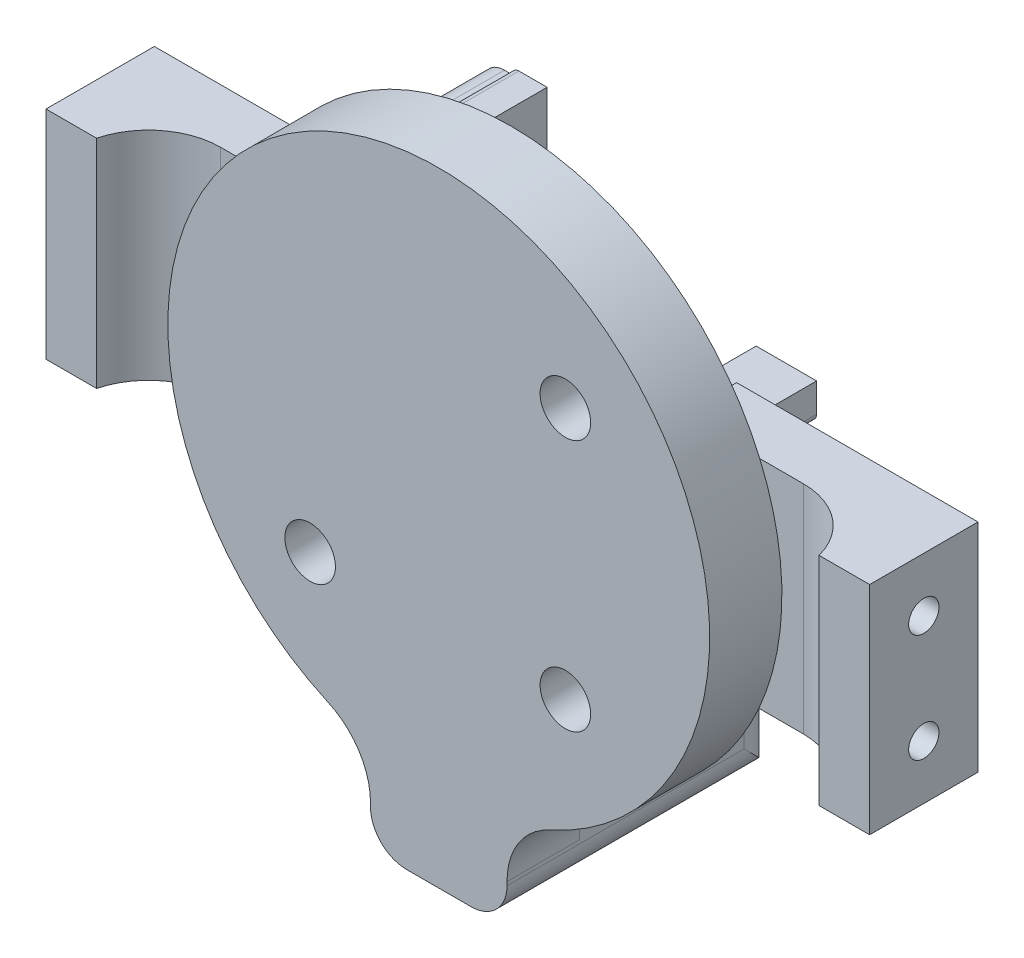
SolidWorks part; units mm, degrees
material "ABS"
ref_plane "Front Plane" through (0, 0, 0) normal (0, 0, 1) x (1, 0, 0)
ref_plane "Top Plane" through (0, 0, 0) normal (0, 1, 0) x (1, 0, 0)
ref_plane "Right Plane" through (0, 0, 0) normal (1, 0, 0) x (0, 0, -1)
sketch "Sketch1" plane through (0, 0, 0) normal (0, 0, 1) x (1, 0, 0)
  line L0 (-17.8145, -17.5408) -> (17.5408, 17.8145)
  line L1 (17.5408, -17.5408) -> (-17.8145, 17.8145)
  circle A0 centre (-0.1369, 0.1369) radius 37.5
  point P0 (17.5408, -17.5408)
  point P1 (-17.8145, -17.5408)
  point P2 (17.5408, 17.8145)
  point P3 (-17.8145, 17.8145)
  dimension "D3" = 75
  dimension "D1" = 35.3553
  dimension "D2" = 35.3553
extrude "Boss-Extrude1" add sketch "Sketch1" along normal blind 10
hole_wizard "CSK for M6 Hex Socket Countersunk Cap Screw1" positions "Sketch4" profile "Sketch5" countersink size "M6" standard "ISO"
sketch "Sketch4" plane through (0, 0, 0) normal (0, 0, -1) x (-1, 0, 0)
  point P0 (-17.3883, 17.5895)
  point P4 (-17.3883, -17.337)
  point P6 (17.9415, -17.337)
sketch "Sketch5" plane through (17.3883, 17.5895, 0) normal (1, 0, 0) x (0, 1, 0)
  line L0 (0, 0) -> (0, 16.543)
  line L1 (0, 16.543) -> (3.5, 14.44)
  line L2 (3.5, 14.44) -> (3.5, 3.22)
  line L3 (3.5, 3.22) -> (6.72, 0)
  line L5 (6.72, 0) -> (0, 0)
  line L6 (-3.5, 3.22) -> (-6.72, 0) construction
  line L10 (0, 16.543) -> (-3.5, 14.44) construction
  line L11 (0, -6.35) -> (0, 107.95) construction
  dimension "Hole Dia." = 7
  dimension "Hole Depth" = 14.44
  dimension "Near C'Sink Dia." = 13.44
  dimension "Near C'Sink Angle" = 90
  dimension "Drill Angle" = 118
ref_plane "Plane1" through (50, 0, 0) normal (1, 0, 0) x (0, 0, -1)
ref_plane "Plane2" through (-50, 0, 0) normal (1, 0, 0) x (0, 0, -1)
sketch "Sketch6" plane through (50, 0, 0) normal (1, 0, 0) x (0, 0, -1)
  line L1 (-7.5, -15) -> (7.5, -15)
  line L2 (-7.5, -15) -> (-7.5, 15)
  line L3 (-7.5, 15) -> (7.5, 15)
  line L4 (7.5, -15) -> (7.5, 15)
  line L5 (-7.5, -15) -> (7.5, 15) construction
  line L6 (-7.5, 15) -> (7.5, -15) construction
  point P0 (0, 0)
  dimension "D1" = 30
  dimension "D2" = 15
extrude "Boss-Extrude2" add sketch "Sketch6" along normal blind 7 separate body
sketch "Sketch7" plane through (-50, 0, 0) normal (1, 0, 0) x (0, 0, -1)
  line L4 (7.5, -15) -> (7.5, 15)
  line L5 (-7.5, -15) -> (7.5, -15)
  line L6 (-7.5, 15) -> (-7.5, -15)
  line L7 (7.5, 15) -> (-7.5, 15)
  line L8 (7.5, -15) -> (7.5, 15)
  line L9 (-7.5, -15) -> (7.5, -15)
  line L10 (-7.5, 15) -> (-7.5, -15)
  line L11 (7.5, 15) -> (-7.5, 15)
  dimension "D1" = 0
extrude "Boss-Extrude3" add sketch "Sketch7" against normal blind 7 separate body
sketch "Sketch8" plane through (0, 0, -7.5) normal (0, 0, -1) x (-1, 0, 0)
  line L0 (-57, 15) -> (-23.5894, 15)
  line L1 (24.1425, 15) -> (11.7405, 15)
  line L4 (57, -15) -> (57, 15) construction
  line L5 (57, -15) -> (24.242, -15)
  line L6 (-57, -15) -> (-57, 15) construction
  line L7 (-57, -15) -> (-57, 15)
  line L8 (57, -15) -> (57, 15)
  line L9 (-11.1873, 15) -> (11.7405, 15)
  line L10 (24.1425, 15) -> (57, 15)
  line L11 (11.641, -15) -> (-11.0878, -15)
  line L12 (-23.6889, -15) -> (-57, -15)
  circle A0 centre (0.1369, 0.1369) radius 37.5 construction
  circle A1 centre (-17.3883, -17.337) radius 6.72 construction
  circle A2 centre (17.9415, -17.337) radius 6.72 construction
  circle A4 centre (-17.3883, 17.5895) radius 6.72 construction
  arc A5 (-34.1724, -15) -> (34.4461, -15) centre (0.1369, 0.1369) ccw
  circle A6 centre (-17.3883, -17.337) radius 6.72
  circle A7 centre (17.9415, -17.337) radius 6.72
  circle A9 centre (-17.3883, 17.5895) radius 6.72
  arc A10 (34.5656, 15) -> (-34.2919, 15) centre (0.1369, 0.1369) ccw
  line M6 (-50, -15) -> (-50, 15)
  line M7 (-50, 15) -> (-57, 15)
  line M8 (-57, 15) -> (-57, -15)
  line M9 (-57, -15) -> (-50, -15)
extrude "Boss-Extrude4" add sketch "Sketch8" against normal up to surface (7.5 mm away) contours M9 M6 M7 M8 | A9 L0 L12 A6 L11 A7 L5 L8 L10 L9 M6 region at (53.5, 0, -7.5) region at (-3.8337, 0.1834, -7.5) up to face at (10.6683, 17.5895, 0)
fillet "Fillet1" radius 10 2 edges at (-50, 0, 0) (50, 0, 0)
sketch "Sketch9" plane through (57, 0, 0) normal (1, 0, 0) x (0, 0, -1)
  line L0 (7.5, 15) -> (7.5, -15) construction
  circle A0 centre (0, -7.5) radius 2.1
  circle A1 centre (0, 7.5) radius 2.1
  point P7 (7.5, 0)
  dimension "D1" = 4.2
  dimension "D2" = 4.2
  dimension "D3" = 15
  dimension "D4" = 7.5
extrude "Cut-Extrude1" cut sketch "Sketch9" against normal blind 6
mirror "Mirror1" about plane through (0, 0, 0) normal (1, 0, 0) of "Cut-Extrude1"
sketch "Sketch11" plane through (0, 0, -7.5) normal (0, 0, -1) x (-1, 0, 0)
  line L0 (27.6369, 7.3869) -> (27.6369, 12.2869)
  line L1 (27.6369, -7.1131) -> (27.6369, -12.0131)
  line L2 (31.5369, 12.2869) -> (27.6369, 12.2869)
  line L3 (0.4369, -7.1131) -> (0.4369, -12.0131)
  line L26 (-4.856, -12.656) -> (-3.5119, -12.656)
  line L27 (-1.656, -12.0131) -> (31.5369, -12.0131)
  line L28 (32.5369, -11.0131) -> (33.5369, -11.0131)
  line L29 (36.5369, -8.0131) -> (36.5369, -6.0131)
  line L30 (33.5369, -3.0131) -> (32.5369, -3.0131)
  line L31 (32.5369, -3.0131) -> (32.5369, 3.3869)
  line L32 (32.5369, 3.3869) -> (33.5369, 3.3869)
  line L33 (36.5369, 6.3869) -> (36.5369, 8.3869)
  line L34 (33.5369, 11.3869) -> (32.5318, 11.3869)
  line L35 (31.5369, 12.2869) -> (20.3869, 12.2869)
  line L36 (20.3869, 12.2869) -> (20.3869, 20.9869)
  line L37 (18.3246, 24.4862) -> (10.718, 26.0155)
  line L38 (1.0557, 26.0155) -> (-6.5509, 24.4862)
  line L39 (-8.6131, 20.9869) -> (-8.6131, 9.5369)
  line L40 (-8.6131, 9.5369) -> (-8.6631, 9.5369)
  line L41 (-9.6631, 8.5369) -> (-9.6631, 4.5369)
  line L42 (-9.6631, 4.5369) -> (0.4369, 4.5369)
  line L43 (0.4369, 4.5369) -> (0.4369, 6.7056)
  line L44 (12.1987, 7.3869) -> (27.6369, 7.3869)
  line L45 (27.6369, 7.3869) -> (27.6369, -7.1131)
  line L46 (27.6369, -7.1131) -> (0.4369, -7.1131)
  line L47 (0.4369, -7.1131) -> (0.4369, -4.2631)
  line L48 (0.4369, -4.2631) -> (-9.6631, -4.2631)
  line L49 (-9.6631, -4.2631) -> (-9.6631, -8.2631)
  line L50 (-8.6631, -9.2631) -> (-7.856, -9.2631)
  line L51 (-7.856, -9.2631) -> (-7.856, -9.656)
  line L52 (-4.856, -12.656) -> (-3.5119, -12.656)
  line L53 (-1.656, -12.0131) -> (31.5369, -12.0131)
  line L54 (32.5369, -11.0131) -> (33.5369, -11.0131)
  line L55 (36.5369, -8.0131) -> (36.5369, -6.0131)
  line L56 (33.5369, -3.0131) -> (32.5369, -3.0131)
  line L57 (32.5369, -3.0131) -> (32.5369, 3.3869)
  line L58 (32.5369, 3.3869) -> (33.5369, 3.3869)
  line L59 (36.5369, 6.3869) -> (36.5369, 8.3869)
  line L60 (33.5369, 11.3869) -> (32.5318, 11.3869)
  line L71 (27.6369, 7.3869) -> (27.6369, -7.1131)
  line L72 (27.6369, -7.1131) -> (0.4369, -7.1131)
  line L73 (0.4369, -7.1131) -> (0.4369, -4.2631)
  line L74 (0.4369, -4.2631) -> (-9.6631, -4.2631)
  line L75 (-9.6631, -4.2631) -> (-9.6631, -8.2631)
  line L76 (-8.6631, -9.2631) -> (-7.856, -9.2631)
  line L77 (-7.856, -9.2631) -> (-7.856, -9.656)
  circle A0 centre (-4.017, -8.5603) radius 1.8 construction
  circle A1 centre (32.4372, 7.3869) radius 1.8 construction
  circle A2 centre (32.4372, -7.0131) radius 1.8 construction
  circle A3 centre (-4.017, -8.5603) radius 1.8
  circle A4 centre (32.4372, 7.3869) radius 1.8
  circle A5 centre (32.4372, -7.0131) radius 1.8
  circle A6 centre (32.4372, -7.0131) radius 2.1
  circle A7 centre (32.4372, 7.3869) radius 2.1
  circle A8 centre (-4.017, -8.5603) radius 2.1
  arc A14 (-3.5119, -12.656) -> (-1.656, -12.0131) centre (-3.5119, -9.656) ccw
  arc A15 (31.5369, -12.0131) -> (32.5369, -11.0131) centre (31.5369, -11.0131) ccw
  arc A16 (33.5369, -11.0131) -> (36.5369, -8.0131) centre (33.5369, -8.0131) ccw
  arc A17 (36.5369, -6.0131) -> (33.5369, -3.0131) centre (33.5369, -6.0131) ccw
  arc A18 (33.5369, 3.3869) -> (36.5369, 6.3869) centre (33.5369, 6.3869) ccw
  arc A19 (36.5369, 8.3869) -> (33.5369, 11.3869) centre (33.5369, 8.3869) ccw
  arc A20 (32.5318, 11.3869) -> (31.5369, 12.2869) centre (31.5369, 11.2869) ccw
  arc A21 (20.3869, 20.9869) -> (18.3246, 24.4862) centre (16.3869, 20.9869) ccw
  arc A22 (10.718, 26.0155) -> (1.0557, 26.0155) centre (5.8869, 14.4869) ccw
  arc A23 (-6.5509, 24.4862) -> (-8.6131, 20.9869) centre (-4.6131, 20.9869) ccw
  arc A24 (-8.6631, 9.5369) -> (-9.6631, 8.5369) centre (-8.6631, 8.5369) ccw
  arc A25 (12.1987, 7.3869) -> (0.4369, 6.7056) centre (5.8869, 14.4869) ccw
  arc A26 (-9.6631, -8.2631) -> (-8.6631, -9.2631) centre (-8.6631, -8.2631) ccw
  arc A27 (-7.856, -9.656) -> (-4.856, -12.656) centre (-4.856, -9.656) ccw
  arc A28 (-3.5119, -12.656) -> (-1.656, -12.0131) centre (-3.5119, -9.656) ccw
  arc A29 (31.5369, -12.0131) -> (32.5369, -11.0131) centre (31.5369, -11.0131) ccw
  arc A30 (33.5369, -11.0131) -> (36.5369, -8.0131) centre (33.5369, -8.0131) ccw
  arc A31 (36.5369, -6.0131) -> (33.5369, -3.0131) centre (33.5369, -6.0131) ccw
  arc A32 (33.5369, 3.3869) -> (36.5369, 6.3869) centre (33.5369, 6.3869) ccw
  arc A33 (36.5369, 8.3869) -> (33.5369, 11.3869) centre (33.5369, 8.3869) ccw
  arc A34 (32.5318, 11.3869) -> (31.5369, 12.2869) centre (31.5369, 11.2869) ccw
  arc A40 (-9.6631, -8.2631) -> (-8.6631, -9.2631) centre (-8.6631, -8.2631) ccw
  arc A41 (-7.856, -9.656) -> (-4.856, -12.656) centre (-4.856, -9.656) ccw
  arc M41 (11.641, -15) -> (24.242, -15) centre (17.9415, -17.337) cw
  dimension "D1" = 0
extrude "Boss-Extrude5" add sketch "Sketch11" along normal blind 25 contours L60 A34 L2 L0 L71 L1 L53 A29 L54 A30 L55 A31 L56 L57 L58 A32 L59 A33 A6 A7 | L77 A41 L52 A28 L53 L1 L72 L73 L74 L75 A40 L76 A8 M41 region at (-31.2693, 0.1466, -7.5) region at (-0.3055, -9.5631, -7.5)
sketch "Sketch12" plane through (0, 0, -32.5) normal (0, 0, -1) x (-1, 0, 0)
  line L1 (2.1729, 1.1091) -> (-1.2992, 1.1091)
  line L2 (2.1729, 1.1091) -> (2.1729, -9.6353)
  line L3 (2.1729, -9.6353) -> (-1.2992, -9.6353)
  line L4 (-1.2992, 1.1091) -> (-1.2992, -9.6353)
  line L5 (2.1729, 1.1091) -> (-1.2992, -9.6353) construction
  line L6 (2.1729, -9.6353) -> (-1.2992, 1.1091) construction
  point P0 (0.4369, -4.2631)
extrude "Cut-Extrude2" cut sketch "Sketch12" against normal up to surface (25 mm away) up to face at (3.367, -2.5365, -7.5)
sketch "Sketch14" plane through (0, 0, 0) normal (0, 0, -1) x (-1, 0, 0)
  line L0 (4.3586, -38.7052) -> (-4.0849, -38.7052) construction
  line L1 (4.3586, -38.7052) -> (-4.0849, -38.7052)
sketch "Sketch15" plane through (0, 0, 0) normal (0, 0, -1) x (-1, 0, 0)
  line L0 (4.3586, -38.7052) -> (-4.0849, -38.7052) construction
  line L1 (9.5851, -28.7052) -> (-9.3114, -28.7052)
  line L2 (9.5851, -28.7052) -> (9.5851, -48.7052)
  line L3 (9.5851, -48.7052) -> (-9.3114, -48.7052)
  line L4 (-9.3114, -28.7052) -> (-9.3114, -48.7052)
  line L5 (9.5851, -28.7052) -> (-9.3114, -48.7052) construction
  line L6 (9.5851, -48.7052) -> (-9.3114, -28.7052) construction
  line L7 (9.5851, -38.7052) -> (-9.3114, -38.7052)
  point P0 (0.1369, -38.7052)
  arc M7 (-34.1724, -15) -> (34.4461, -15) centre (0.1369, 0.1369) ccw
  dimension "D1" = 10
extrude "Boss-Extrude7" add sketch "Sketch15" against normal up to surface (10 mm away) contours L2 L7 L4 L3 | L1 L4 L2 M7 | L2 L1 L4 L3 region at (-0.1369, -32.8417, 0) region at (-0.1369, -43.7052, 0) up to face at (20.8883, 17.5895, 10)
extrude "Boss-Extrude8" add sketch "Sketch15<4>" along normal blind 27.8 contours L2 L7 L4 L3 region at (-0.1369, -43.7052, 0)
sketch "Sketch15<4>" plane through (0, 0, 0) normal (0, 0, -1) x (-1, 0, 0) same geometry as "Sketch15"
sketch "Sketch16" plane through (0, -38.7052, 0) normal (0, 1, 0) x (1, 0, 0)
  circle A0 centre (-0.1369, 21.7) radius 3.175 construction
  circle A1 centre (-0.1369, 21.7) radius 3.175
sketch "Sketch17" plane through (0, -48.7052, 0) normal (0, -1, 0) x (1, 0, 0)
  circle A0 centre (-0.1369, -21.7) radius 3.175 construction
  circle A1 centre (-0.1369, -21.7) radius 3.175
hole_wizard "1/4 (0.25) Diameter Hole2" positions "Sketch22" profile "Sketch23" hole size "1/4" standard "ANSI Inch"
sketch "Sketch22" plane through (0, -48.7052, 0) normal (0, -1, 0) x (-1, 0, 0)
  point P0 (0.1369, 21.7)
sketch "Sketch23" plane through (-0.1369, -48.7052, -21.7) normal (1, 0, 0) x (0, 0, -1)
  line L0 (0, 0) -> (0, 16.9077)
  line L1 (0, 16.9077) -> (3.175, 15)
  line L2 (3.175, 15) -> (3.175, 0)
  line L5 (3.175, 0) -> (0, 0)
  line L10 (0, 16.9077) -> (-3.175, 15) construction
  line L11 (0, -6.35) -> (0, 107.95) construction
  dimension "Hole Dia." = 6.35
  dimension "Hole Depth" = 15
  dimension "Drill Angle" = 118
sketch "Sketch24" plane through (0, 0, 0) normal (0, 0, -1) x (-1, 0, 0)
  line L0 (9.5851, -38.7052) -> (9.5851, -15)
  line L1 (11.641, -15) -> (-11.0878, -15) construction
  line L2 (-9.3114, -38.7052) -> (-9.3114, -15)
  line L3 (9.5851, -15) -> (-9.3114, -15)
  line L4 (9.5851, -38.7052) -> (-9.3114, -38.7052)
extrude "Boss-Extrude9" add sketch "Sketch24" along normal blind 11.55
fillet "Fillet2" radius 10 2 edges at (9.3114, -36.1534, 5) (-9.5851, -36.1534, 5)
fillet "Fillet4" radius 5 4 edges at (-9.5851, -43.7052, -27.8) (9.3114, -43.7052, -27.8) (-9.5851, -48.7052, -8.9) (9.3114, -48.7052, -8.9)
sketch "Sketch25" plane through (0, -38.7052, 0) normal (0, 1, 0) x (1, 0, 0)
  line L4 (4.3114, 27.8) -> (-4.5851, 27.8)
  line L5 (-9.5851, 22.8) -> (-9.5851, 11.55)
  line L6 (-9.5851, 11.55) -> (9.3114, 11.55)
  line L7 (9.3114, 11.55) -> (9.3114, 22.8)
  line L8 (4.3114, 27.8) -> (-4.5851, 27.8)
  line L9 (-9.5851, 22.8) -> (-9.5851, 11.55)
  line L10 (-9.5851, 11.55) -> (9.3114, 11.55)
  line L11 (9.3114, 11.55) -> (9.3114, 22.8)
  circle A0 centre (-0.1369, 21.7) radius 3.175 construction
  circle A1 centre (-0.1369, 21.7) radius 3.175
  arc A2 (-4.5851, 27.8) -> (-9.5851, 22.8) centre (-4.5851, 22.8) ccw
  arc A3 (9.3114, 22.8) -> (4.3114, 27.8) centre (4.3114, 22.8) ccw
  arc A4 (-4.5851, 27.8) -> (-9.5851, 22.8) centre (-4.5851, 22.8) ccw
  arc A5 (9.3114, 22.8) -> (4.3114, 27.8) centre (4.3114, 22.8) ccw
  dimension "D1" = 0
sketch "yAxis" plane through (0, 0, 10) normal (0, 0, 1) x (1, 0, 0)
  line L0 (0, -67.43) -> (-0.1369, 0.1369)
  line L3 (-9.5851, -43.1992) -> (-9.5851, -43.7052)
  line L4 (-4.5851, -48.7052) -> (4.3114, -48.7052)
  line L5 (9.3114, -43.7052) -> (9.3114, -43.1992)
  line L6 (-9.5851, -43.1992) -> (-9.5851, -43.7052)
  line L7 (-4.5851, -48.7052) -> (4.3114, -48.7052)
  line L8 (9.3114, -43.7052) -> (9.3114, -43.1992)
  circle A0 centre (17.3883, 17.5895) radius 3.5 construction
  circle A1 centre (17.3883, -17.337) radius 3.5 construction
  circle A2 centre (-17.9415, -17.337) radius 3.5 construction
  circle A3 centre (17.3883, 17.5895) radius 3.5
  circle A4 centre (17.3883, -17.337) radius 3.5
  arc A5 (-9.5851, -43.7052) -> (-4.5851, -48.7052) centre (-4.5851, -43.7052) ccw
  arc A6 (4.3114, -48.7052) -> (9.3114, -43.7052) centre (4.3114, -43.7052) ccw
  arc A7 (15.2171, -34.0758) -> (9.3114, -43.1992) centre (19.3114, -43.1992) ccw
  arc A8 (15.2171, -34.0758) -> (-15.4908, -34.0758) centre (-0.1369, 0.1369) ccw
  arc A9 (-9.5851, -43.1992) -> (-15.4908, -34.0758) centre (-19.5851, -43.1992) ccw
  arc A10 (-9.5851, -43.7052) -> (-4.5851, -48.7052) centre (-4.5851, -43.7052) ccw
  arc A11 (4.3114, -48.7052) -> (9.3114, -43.7052) centre (4.3114, -43.7052) ccw
  arc A12 (15.2171, -34.0758) -> (9.3114, -43.1992) centre (19.3114, -43.1992) ccw
  arc A13 (15.2171, -34.0758) -> (-15.4908, -34.0758) centre (-0.1369, 0.1369) ccw
  arc A14 (-9.5851, -43.1992) -> (-15.4908, -34.0758) centre (-19.5851, -43.1992) ccw
  circle A15 centre (-17.9415, -17.337) radius 3.5
  dimension "D1" = 0
sketch "xAxis" plane through (0, 0, 10) normal (0, 0, 1) x (1, 0, 0)
  line L0 (-0.1369, 0.1369) -> (68.5182, 0.1369)
ref_axis "x" through (-0.1369, 0.1369, 10) along (1, 0, 0)
ref_axis "y" through (0, -67.43, 10) along (-0.002, 1, 0)
